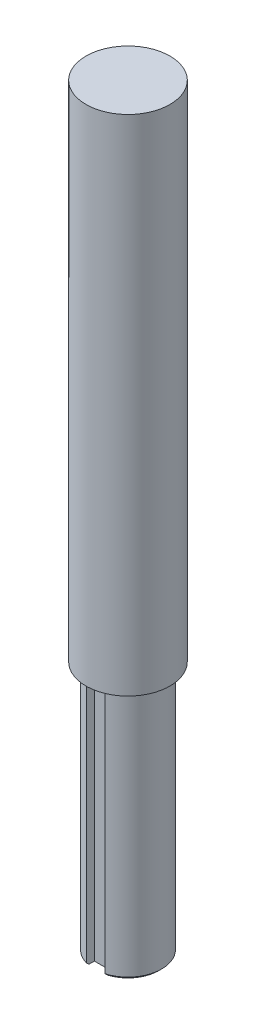
SolidWorks part; units mm, degrees
ref_plane "Front Plane" through (0, 0, 0) normal (0, 0, 1) x (1, 0, 0)
ref_plane "Top Plane" through (0, 0, 0) normal (0, 1, 0) x (1, 0, 0)
ref_plane "Right Plane" through (0, 0, 0) normal (1, 0, 0) x (0, 0, -1)
sketch "Sketch1" plane through (0, 0, 0) normal (0, 0, 1) x (1, 0, 0)
  line L0 (0, 0) -> (4, 0)
  line L1 (4, 0) -> (4, 30)
  line L2 (4, 30) -> (5, 30)
  line L3 (5, 30) -> (5, 90)
  line L4 (5, 90) -> (0, 90)
  line L5 (0, 90) -> (0, 0)
  dimension "D1" = 4
  dimension "D2" = 5
  dimension "D3" = 30
  dimension "D4" = 90
revolve "Revolve1" add sketch "Sketch1" angle 360 about L5
chamfer "Chamfer1" distance 0.3 angle 45 1 edges at (-4, 0, 0)
sketch "Sketch2" plane through (0, 0, 0) normal (0, -1, 0) x (1, 0, 0)
  line L1 (-1.125, 5.125) -> (1.125, 5.125)
  line L2 (-1.125, 5.125) -> (-1.125, 2.875)
  line L3 (-1.125, 2.875) -> (1.125, 2.875)
  line L4 (1.125, 5.125) -> (1.125, 2.875)
  line L5 (-1.125, 5.125) -> (1.125, 2.875) construction
  line L6 (-1.125, 2.875) -> (1.125, 5.125) construction
  circle A0 centre (0, 0) radius 4 construction
  circle A1 centre (0, 0) radius 4 construction
  point P0 (0, 4)
  dimension "D1" = 2.25
extrude "Cut-Extrude1" cut sketch "Sketch2" against normal up to surface (30 mm away) up to face at (-5, 30, 0)
ref_axis "Axis1" through (0, 30, 0) along (0, 1, 0)
